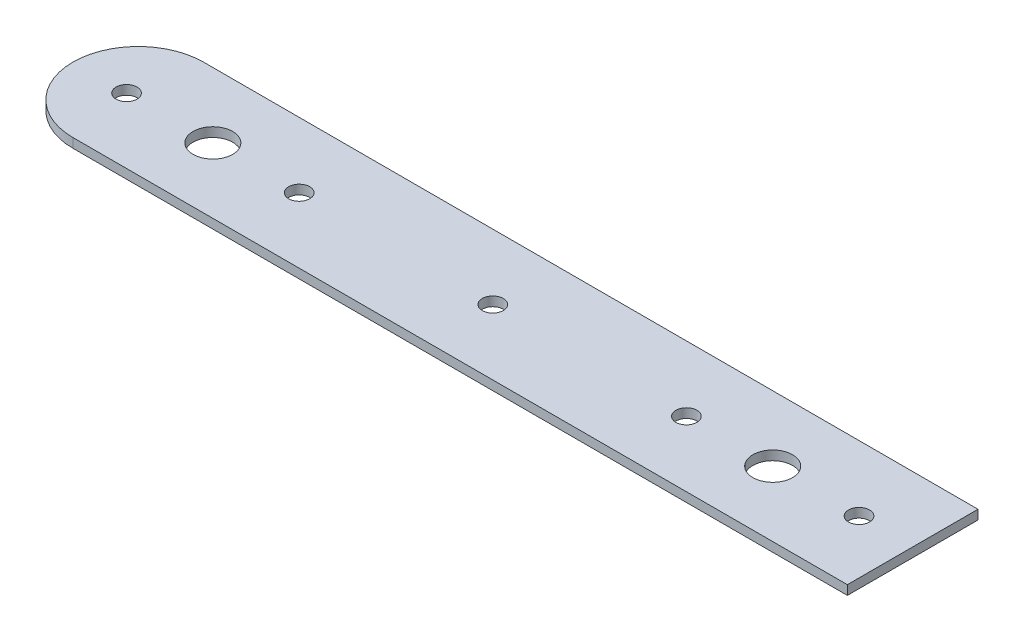
SolidWorks part; units mm, degrees
ref_plane "前视" through (0, 0, 0) normal (0, 0, 1) x (1, 0, 0)
ref_plane "上视" through (0, 0, 0) normal (0, 1, 0) x (1, 0, 0)
ref_plane "右视" through (0, 0, 0) normal (1, 0, 0) x (0, 0, -1)
sketch "草图1" plane through (0, 0, 0) normal (0, 1, 0) x (1, 0, 0)
  line L1 (-90, 14) -> (90, 14)
  line L2 (-90, 14) -> (-90, -14)
  line L3 (-90, -14) -> (90, -14)
  line L4 (90, 14) -> (90, -14)
  line L5 (-90, 14) -> (90, -14) construction
  line L6 (-90, -14) -> (90, 14) construction
  point P0 (0, 0)
  dimension "D1" = 180
  dimension "D2" = 28
extrude "凸台-拉伸1" add sketch "草图1" along normal blind 2 contours L2 | L2 | L3 L1 | L4 | L4 region at (0, 0, 0)
sketch "草图2" plane through (0, 2, 0) normal (0, 1, 0) x (1, 0, 0)
  circle A0 centre (-60, 0) radius 4.25
  circle A1 centre (60, 0) radius 4.25
  circle A2 centre (0, 0) radius 2.25
  dimension "D1" = 8.5
  dimension "D2" = 8.5
  dimension "D5" = 4.5
  dimension "D3" = 120
  dimension "D4" = 60
extrude "切除-拉伸1" cut sketch "草图2" against normal up to next
fillet "圆角1" 2 edges at (-90, 1, 14) (-90, 1, -14) type full round first side face at (0, 1, 14) second side face at (0, 1, -14) middle face at (-90, 1, 0)
sketch "草图3" plane through (0, 2, 0) normal (0, 1, 0) x (1, 0, 0)
  circle A0 centre (-78.5, 0) radius 2.25
  circle A1 centre (-41.5, 0) radius 2.25
  circle A2 centre (41.5, 0) radius 2.25
  circle A3 centre (78.5, 0) radius 2.25
  circle A4 centre (-60, 0) radius 4.25 construction
  circle A5 centre (60, 0) radius 4.25 construction
  dimension "D2" = 18.5
  dimension "D3" = 4.5
  dimension "D4" = 4.5
  dimension "D6" = 18.5
  dimension "D7" = 4.5
  dimension "D8" = 4.5
  dimension "D1" = 37
  dimension "D5" = 37
extrude "切除-拉伸2" cut sketch "草图3" against normal up to next
